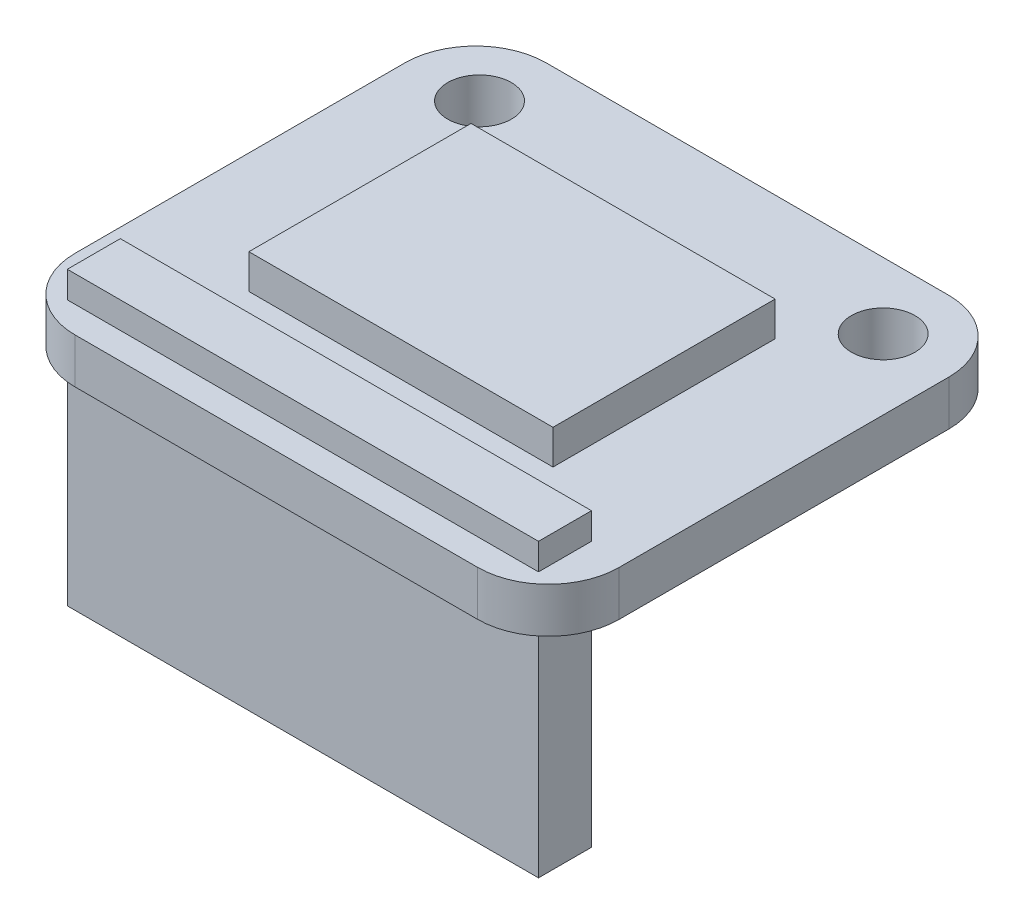
SolidWorks part; units mm, degrees
ref_plane "Front Plane" through (0, 0, 0) normal (0, 0, 1) x (1, 0, 0)
ref_plane "Top Plane" through (0, 0, 0) normal (0, 1, 0) x (1, 0, 0)
ref_plane "Right Plane" through (0, 0, 0) normal (1, 0, 0) x (0, 0, -1)
sketch "Sketch1" plane through (0, 0, 0) normal (0, 1, 0) x (1, 0, 0)
  line L1 (-7.595, -8.89) -> (7.595, -8.89)
  line L2 (-10.265, -6.22) -> (-10.265, 6.22)
  line L3 (-7.595, 8.89) -> (7.595, 8.89)
  line L4 (10.265, -6.22) -> (10.265, 6.22)
  line L5 (-10.265, -8.89) -> (10.265, 8.89) construction
  line L6 (-10.265, 8.89) -> (10.265, -8.89) construction
  arc A0 (-7.595, -8.89) -> (-10.265, -6.22) centre (-7.595, -6.22) cw
  arc A1 (7.595, -8.89) -> (10.265, -6.22) centre (7.595, -6.22) ccw
  arc A2 (7.595, 8.89) -> (10.265, 6.22) centre (7.595, 6.22) cw
  arc A3 (-10.265, 6.22) -> (-7.595, 8.89) centre (-7.595, 6.22) cw
  point P0 (0, 0)
  dimension "D3" = 2.67
  dimension "D1" = 17.78
  dimension "D2" = 20.53
extrude "Boss-Extrude1" add sketch "Sketch1" along normal blind 1.7
sketch "Sketch2" plane through (0, 1.7, 0) normal (0, 1, 0) x (1, 0, 0)
  line L1 (-5.7376, -4.191) -> (5.7376, -4.191)
  line L2 (-5.7376, -4.191) -> (-5.7376, 4.191)
  line L3 (-5.7376, 4.191) -> (5.7376, 4.191)
  line L4 (5.7376, -4.191) -> (5.7376, 4.191)
  line L5 (-5.7376, -4.191) -> (5.7376, 4.191) construction
  line L6 (-5.7376, 4.191) -> (5.7376, -4.191) construction
  point P0 (0, 0)
extrude "Boss-Extrude2" add sketch "Sketch2" along normal offset from surface (1.3 mm away) 3 up to face at (0, 0, 0)
sketch "Sketch3" plane through (0, 1.7, 0) normal (0, 1, 0) x (1, 0, 0)
  line L0 (-6.415, 6.39) -> (6.415, 6.39) construction
  line L1 (0, 8.89) -> (0, 6.39) construction
  line L2 (7.595, 8.89) -> (-7.595, 8.89) construction
  line L3 (-7.615, 7.59) -> (-7.615, 8.89) construction
  circle A0 centre (-7.615, 6.39) radius 1.2
  circle A1 centre (7.615, 6.39) radius 1.2
  dimension "D1" = 2.4
  dimension "D2" = 12.83
  dimension "D3" = 1.3
extrude "Cut-Extrude1" cut sketch "Sketch3" against normal through all
sketch "Sketch4" plane through (0, 1.7, 0) normal (0, 1, 0) x (1, 0, 0)
  line L0 (0, -5.89) -> (0, 0) construction
  line L1 (-8.89, -5.89) -> (8.89, -5.89)
  line L2 (-8.89, -5.89) -> (-8.89, -7.89)
  line L3 (-8.89, -7.89) -> (8.89, -7.89)
  line L4 (8.89, -5.89) -> (8.89, -7.89)
  line L5 (-7.595, -8.89) -> (7.595, -8.89) construction
  dimension "D1" = 2
  dimension "D2" = 17.78
  dimension "D3" = 1
extrude "Boss-Extrude3" add sketch "Sketch4" along normal blind 1 and the other way blind 10
sketch "Sketch5" plane through (0, 3, 0) normal (0, 1, 0) x (1, 0, 0)
  line L0 (-5.7376, 4.191) -> (5.7376, -4.191) construction
  point P4 (0, 0)
  point P5 (0, 0)
ref_axis "Axis1" through (-8.7841, 3, 0) along (1, 0, 0)
